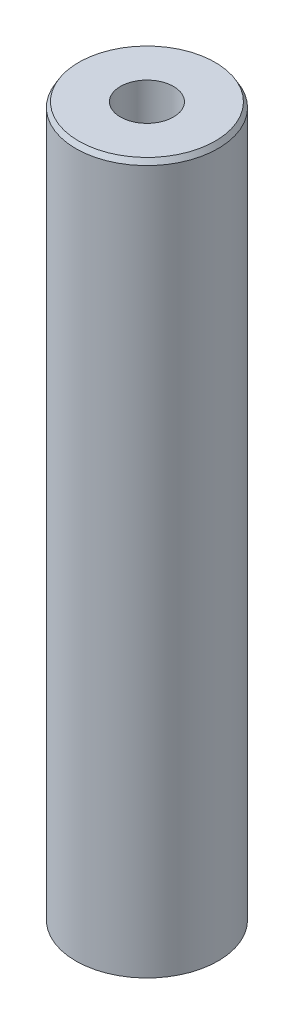
SolidWorks part; units mm, degrees
ref_plane "Front Plane" through (0, 0, 0) normal (0, 0, 1) x (1, 0, 0)
ref_plane "Top Plane" through (0, 0, 0) normal (0, 1, 0) x (1, 0, 0)
ref_plane "Right Plane" through (0, 0, 0) normal (1, 0, 0) x (0, 0, -1)
sketch "Sketch1" plane through (0, 0, 0) normal (0, 1, 0) x (1, 0, 0)
  circle A0 centre (0, 0) radius 60
  dimension "SHAFT_OD" = 120
extrude "Boss-Extrude1" add sketch "Sketch1" along normal blind 600
sketch "Sketch2" plane through (0, 0, 0) normal (0, 1, 0) x (1, 0, 0)
  circle A0 centre (0, 0) radius 22.3791
  dimension "BORE_D" = 44.7581
extrude "Cut-Extrude1" cut sketch "Sketch2" along normal through all
chamfer "Chamfer1" distance 4.2375 angle 30 2 edges at (0, 600, 60) (0, 0, 60) first distance on face at (0, 600, 60) first distance on face at (0, 0, 22.3791)
